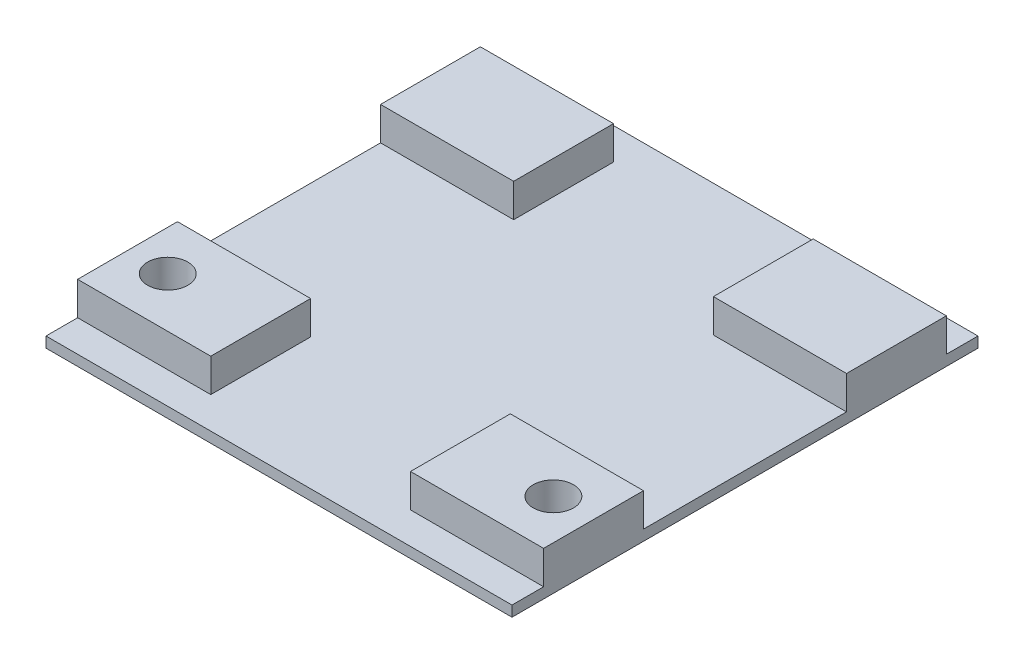
SolidWorks part; units mm, degrees
ref_plane "Front Plane" through (0, 0, 0) normal (0, 0, 1) x (1, 0, 0)
ref_plane "Top Plane" through (0, 0, 0) normal (0, 1, 0) x (1, 0, 0)
ref_plane "Right Plane" through (0, 0, 0) normal (1, 0, 0) x (0, 0, -1)
sketch "Sketch1" plane through (0, 0, 0) normal (0, 1, 0) x (1, 0, 0)
  line L1 (-70, -70) -> (70, -70)
  line L2 (-70, -70) -> (-70, 70)
  line L3 (-70, 70) -> (70, 70)
  line L4 (70, -70) -> (70, 70)
  line L5 (-70, -70) -> (70, 70) construction
  line L6 (-70, 70) -> (70, -70) construction
  point P0 (0, 0)
  dimension "D1" = 140
  dimension "D2" = 140
extrude "Boss-Extrude1" add sketch "Sketch1" along normal blind 3.175
sketch "Sketch2" plane through (0, 3.175, 0) normal (0, 1, 0) x (1, 0, 0)
  line L0 (0, -1.7463) -> (0, 1.7463) construction
  line L1 (-45, -30.5) -> (45, -30.5) construction
  line L2 (-45, -30.5) -> (-45, 30.5) construction
  line L3 (-45, 30.5) -> (45, 30.5) construction
  line L4 (45, -30.5) -> (45, 30.5) construction
  line L5 (-45, -30.5) -> (45, 30.5) construction
  line L6 (-45, 30.5) -> (45, -30.5) construction
  line L11 (60, -30.5) -> (30, -30.5)
  line L12 (-60, -60.5) -> (-30, -60.5)
  line L21 (-60, -60.5) -> (-60, -30.5)
  line L22 (-60, -30.5) -> (-30, -30.5)
  line L23 (30, -60.5) -> (30, -30.5)
  line L24 (-30, -60.5) -> (-30, -30.5)
  line L25 (-60, -60.5) -> (-30, -30.5) construction
  line L26 (-60, -30.5) -> (-30, -60.5) construction
  line L27 (60, -60.5) -> (30, -60.5)
  line L28 (60, -60.5) -> (60, -30.5)
  line L29 (-1.7463, 0) -> (1.7463, 0) construction
  line L34 (-60, 30.5) -> (-30, 30.5)
  line L35 (-30, 60.5) -> (-30, 30.5)
  line L36 (-60, 60.5) -> (-30, 60.5)
  line L37 (-60, 60.5) -> (-60, 30.5)
  line L38 (-60, -30.5) -> (-70, -30.5) construction
  line L39 (-70, 70) -> (-70, -70) construction
  circle A0 centre (0, 0) radius 40 construction
  point P0 (0, 0)
  point P8 (-45, -45.5)
  dimension "D3" = 80
  dimension "D1" = 90
  dimension "D2" = 61
  dimension "D4" = 30
  dimension "D5" = 30
extrude "Boss-Extrude2" add sketch "Sketch2" along normal blind 10
sketch "Sketch5" plane through (0, 0, -30.5) normal (0, 0, 1) x (1, 0, 0)
  line L0 (-30, 3.175) -> (-60, 3.175) construction
  line L1 (-60, 13.175) -> (-53.3668, 3.175) construction
  line L2 (-30, 13.175) -> (-30, 3.175) construction
  line L3 (-60, 13.175) -> (-30, 13.175)
  line L4 (0, 0) -> (0, 13.8602) construction
  line L5 (0, -7.2462) -> (0, 7.2462) construction
  line L6 (-30, 13.175) -> (-30, 3.175)
  line L7 (-60, 13.175) -> (-30, 13.175)
  line L12 (-30, 13.175) -> (-30, 9.675)
  line L13 (-60, 13.175) -> (-30, 13.175)
  line L14 (-60, 3.175) -> (-30, 3.175) construction
  line L15 (-60, 3.175) -> (-60, 9.675) construction
  line L16 (-60, 9.675) -> (-30, 9.675) construction
  line L17 (-30, 3.175) -> (-30, 9.675) construction
  line L18 (-60, 3.175) -> (-30, 9.675) construction
  line L19 (-60, 9.675) -> (-30, 3.175) construction
  line L20 (-60, 13.175) -> (-30, 13.175)
  line L21 (-30, 13.175) -> (-30, 9.675)
  spline S0 degree 3 poles (-60, 13.175) (-57.6822, 9.6807) (-40.0678, 9.675) (-30, 9.675) knots 0 0 0 0 1 1 1 1
  point P21 (-45, 6.425)
  dimension "D1" = 12
  dimension "6.5" = 6.5
sketch "Sketch11" plane through (-60, 0, 0) normal (-1, 0, 0) x (0, 0, 1)
  line L1 (30.5, 3.175) -> (60.5, 3.175)
  line L2 (30.5, 3.175) -> (30.5, 13.175)
  line L3 (30.5, 13.175) -> (60.5, 13.175)
  line L4 (60.5, 3.175) -> (60.5, 13.175)
  line L5 (30.5, 3.175) -> (60.5, 13.175) construction
  line L6 (30.5, 13.175) -> (60.5, 3.175) construction
  point P4 (45.5, 8.175)
extrude "Boss-Extrude3" add sketch "Sketch11" along normal up to surface (10 mm away) up to face at (-70, 1.5875, 0)
sketch "Sketch13" plane through (60, 0, 0) normal (1, 0, 0) x (0, 0, -1)
  line L1 (-60.5, 3.175) -> (-30.5, 3.175)
  line L2 (-60.5, 3.175) -> (-60.5, 13.175)
  line L3 (-60.5, 13.175) -> (-30.5, 13.175)
  line L4 (-30.5, 3.175) -> (-30.5, 13.175)
  line L5 (-60.5, 3.175) -> (-30.5, 13.175) construction
  line L6 (-60.5, 13.175) -> (-30.5, 3.175) construction
  point P4 (-45.5, 8.175)
extrude "Boss-Extrude4" add sketch "Sketch13" along normal up to surface (10 mm away) up to face at (70, 1.5875, 0)
mirror "Mirror1" about plane through (0, 0, 0) normal (1, 0, 0) of "Boss-Extrude2"
sketch "Sketch16" plane through (60, 0, 0) normal (1, 0, 0) x (0, 0, -1)
  line L1 (30.5, 3.175) -> (60.5, 3.175)
  line L2 (30.5, 3.175) -> (30.5, 13.175)
  line L3 (30.5, 13.175) -> (60.5, 13.175)
  line L4 (60.5, 3.175) -> (60.5, 13.175)
  line L5 (30.5, 3.175) -> (60.5, 13.175) construction
  line L6 (30.5, 13.175) -> (60.5, 3.175) construction
  point P4 (45.5, 8.175)
extrude "Boss-Extrude6" add sketch "Sketch16" along normal up to surface (10 mm away) up to face at (70, 4.8813, 22.75)
sketch "Sketch17" plane through (-60, 0, 0) normal (-1, 0, 0) x (0, 0, 1)
  line L1 (-60.5, 3.175) -> (-30.5, 3.175)
  line L2 (-60.5, 3.175) -> (-60.5, 13.175)
  line L3 (-60.5, 13.175) -> (-30.5, 13.175)
  line L4 (-30.5, 3.175) -> (-30.5, 13.175)
  line L5 (-60.5, 3.175) -> (-30.5, 13.175) construction
  line L6 (-60.5, 13.175) -> (-30.5, 3.175) construction
  point P4 (-45.5, 8.175)
extrude "Boss-Extrude7" add sketch "Sketch17" along normal up to surface (10 mm away) up to face at (-70, 4.8813, 22.75)
sketch "Sketch18" plane through (0, 13.175, 0) normal (0, 1, 0) x (1, 0, 0)
  line L0 (-30, -30.5) -> (-70, -30.5) construction
  line L1 (-30, -60.5) -> (-60, -60.5) construction
  line L2 (-30, -60.5) -> (-30, -30.5) construction
  line L3 (-30, -30.5) -> (-60, -30.5) construction
  line L4 (-60, -60.5) -> (-60, -30.5) construction
  line L5 (-30, -60.5) -> (-60, -30.5) construction
  line L6 (-30, -30.5) -> (-60, -60.5) construction
  line L8 (-45, -30.5) -> (-45, 30.5) construction
  line L9 (-70, 30.5) -> (-30, 30.5) construction
  line L10 (-51.4643, 30.5) -> (-51.4643, -60.5) construction
  line L11 (-70, 30.5) -> (-30, 30.5) construction
  line L12 (-45, -45.5) -> (-60, -45.5) construction
  line L13 (0, -7.2462) -> (0, 7.2462) construction
  circle A0 centre (-45, 0) radius 6.4643 construction
  circle A1 centre (-57.9286, -45.5) radius 6.4643 construction
  circle A2 centre (-57.9286, -45.5) radius 6.05
  circle A3 centre (57.9286, -45.5) radius 6.05
  point P4 (-45, -45.5)
  dimension "D2" = 12.9286
  dimension "D3" = 12.9286
  dimension "D4" = 12.1
  dimension "D1" = 30
extrude "Cut-Extrude1" cut sketch "Sketch18" against normal up to surface (13.175 mm away) up to face at (0, 0, 0)
sketch "Sketch20" plane through (0, 0, 0) normal (0, -1, 0) x (-1, 0, 0)
  line L0 (-45, 30.5) -> (-30, 30.5) construction
  line L1 (45, 30.5) -> (-45, 30.5) construction
  line L2 (45, 30.5) -> (45, -30.5) construction
  line L3 (45, -30.5) -> (-45, -30.5) construction
  line L4 (-45, 30.5) -> (-45, -30.5) construction
  line L5 (45, 30.5) -> (-45, -30.5) construction
  line L6 (45, -30.5) -> (-45, 30.5) construction
  line L7 (-30, 30.5) -> (-30, 60.5) construction
  line L8 (-70, -70) -> (-70, 70) construction
  line L9 (-30, 60.5) -> (-70, 60.5) construction
  line L10 (-30, 60.5) -> (-30, 30.5) construction
  line L11 (-30, 30.5) -> (-70, 30.5) construction
  line L12 (-70, 60.5) -> (-70, 30.5) construction
  line L13 (-30, 60.5) -> (-70, 30.5) construction
  line L14 (-30, 30.5) -> (-70, 60.5) construction
  line L15 (-30, 45.5) -> (-70, 45.5) construction
  line L16 (-50, 30.5) -> (-50, 60.5) construction
  line L18 (0, 7.2462) -> (0, -7.2462) construction
  line L19 (-7.2462, 0) -> (7.2462, 0) construction
  circle A0 centre (-35, 56.75) radius 0.8
  circle A1 centre (-65, 56.75) radius 0.8
  circle A2 centre (-65, 34.25) radius 0.8
  circle A3 centre (-35, 34.25) radius 0.8
  circle A4 centre (35, 56.75) radius 0.8
  circle A5 centre (65, 56.75) radius 0.8
  circle A6 centre (65, 34.25) radius 0.8
  circle A7 centre (35, 34.25) radius 0.8
  circle A8 centre (65, -34.25) radius 0.8
  circle A9 centre (35, -34.25) radius 0.8
  circle A10 centre (35, -56.75) radius 0.8
  circle A11 centre (65, -56.75) radius 0.8
  circle A12 centre (-35, -34.25) radius 0.8
  circle A13 centre (-65, -34.25) radius 0.8
  circle A14 centre (-65, -56.75) radius 0.8
  circle A15 centre (-35, -56.75) radius 0.8
  point P0 (0, 0)
  point P10 (-50, 45.5)
  dimension "D5" = 1.6
  dimension "D1" = 90
  dimension "D2" = 61
  dimension "D3" = 15
  dimension "D4" = 30
  dimension "D6" = 5
sketch "Sketch21" plane through (0, 0, 0) normal (0, -1, 0) x (-1, 0, 0)
  line L0 (57.9286, -45.5) -> (57.9286, -55.5) construction
  line L2 (67.9286, -55.5) -> (47.9286, -55.5) construction
  line L3 (67.9286, -55.5) -> (67.9286, -15.5) construction
  line L4 (67.9286, -15.5) -> (47.9286, -15.5) construction
  line L5 (47.9286, -55.5) -> (47.9286, -15.5) construction
  line L6 (67.9286, -55.5) -> (47.9286, -15.5) construction
  line L7 (67.9286, -15.5) -> (47.9286, -55.5) construction
  circle A0 centre (57.9286, -45.5) radius 2.45 construction
  point P8 (57.9286, -35.5)
  point P9 (57.9286, -55.5)
  dimension "D1" = 4.9
  dimension "D2" = 10
  dimension "D3" = 40
  dimension "20" = 20
